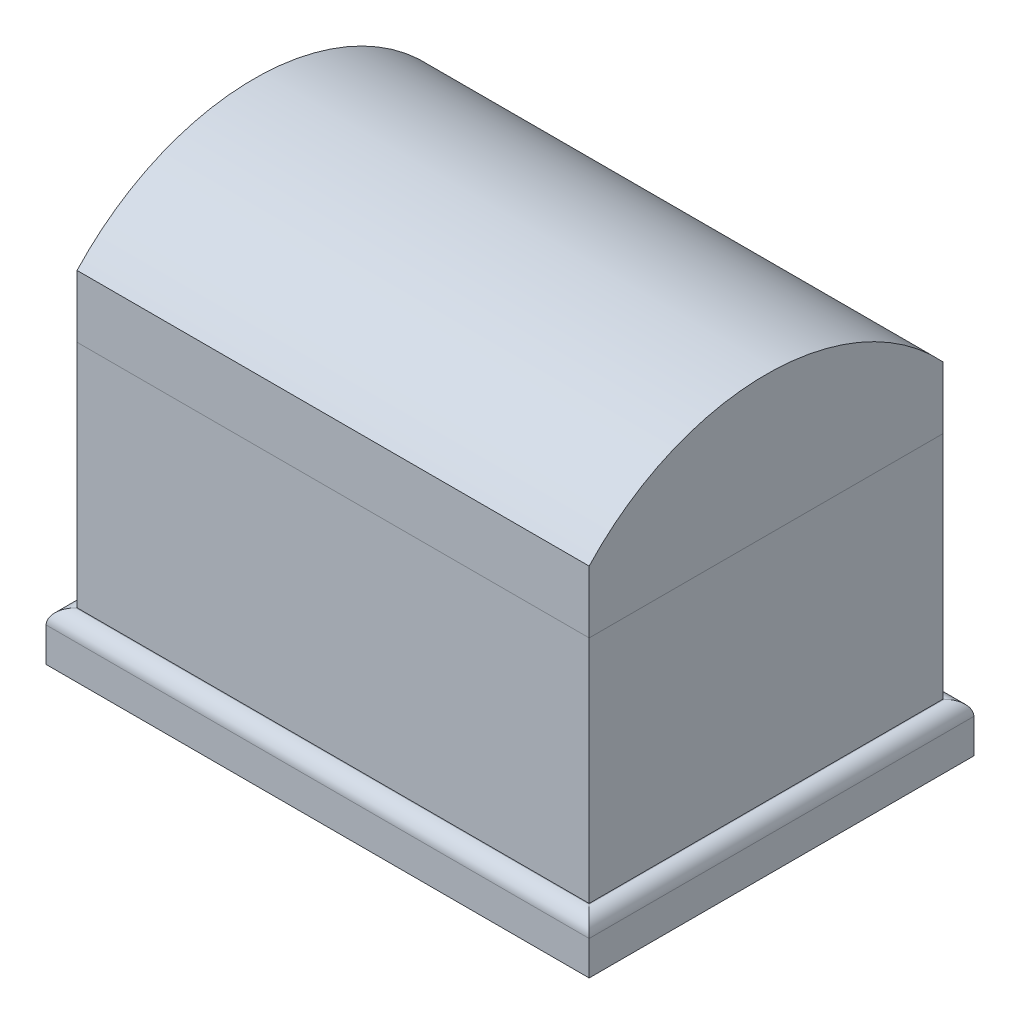
SolidWorks part; units mm, degrees
ref_plane "Front Plane" through (0, 0, 0) normal (0, 0, 1) x (1, 0, 0)
ref_plane "Top Plane" through (0, 0, 0) normal (0, 1, 0) x (1, 0, 0)
ref_plane "Right Plane" through (0, 0, 0) normal (1, 0, 0) x (0, 0, -1)
sketch "Sketch1" plane through (0, 0, 0) normal (0, 1, 0) x (1, 0, 0)
  line L1 (-78.867, -54.483) -> (78.867, -54.483)
  line L2 (-78.867, -54.483) -> (-78.867, 54.483)
  line L3 (-78.867, 54.483) -> (78.867, 54.483)
  line L4 (78.867, -54.483) -> (78.867, 54.483)
  line L5 (-78.867, -54.483) -> (78.867, 54.483) construction
  line L6 (-78.867, 54.483) -> (78.867, -54.483) construction
  point P0 (0, 0)
  dimension "D1" = 157.734
  dimension "D2" = 108.966
extrude "Boss-Extrude1" add sketch "Sketch1" along normal blind 114.1349
sketch "Sketch2" plane through (0, 0, 54.483) normal (0, 0, 1) x (1, 0, 0)
  line L0 (-78.867, 0) -> (-79.0575, 0)
  line L1 (-83.6295, -4.572) -> (-83.6295, -15.113)
  line L2 (-83.6295, -15.113) -> (-73.7235, -15.113)
  line L3 (-73.7235, -15.113) -> (-73.7235, 0)
  line L4 (-78.867, 0) -> (78.867, 0) construction
  line L5 (-73.7235, 0) -> (-78.867, 0)
  arc A0 (-79.0575, 0) -> (-83.6295, -4.572) centre (-79.0575, -4.572) ccw
  point P11 (-83.6295, 0)
  dimension "D4" = 4.572
  dimension "D1" = 9.906
  dimension "D2" = 4.7625
  dimension "D3" = 15.113
sketch "Sketch3" plane through (0, 0, 0) normal (0, -1, 0) x (1, 0, 0)
  line L4 (78.867, -54.483) -> (78.867, 54.483)
  line L5 (78.867, 54.483) -> (-78.867, 54.483)
  line L6 (-78.867, 54.483) -> (-78.867, -54.483)
  line L7 (-78.867, -54.483) -> (78.867, -54.483)
  line L8 (78.867, -54.483) -> (78.867, 54.483)
  line L9 (78.867, 54.483) -> (-78.867, 54.483)
  line L10 (-78.867, 54.483) -> (-78.867, -54.483)
  line L11 (-78.867, -54.483) -> (78.867, -54.483)
  dimension "D1" = 0
sweep "Sweep1" add profiles "Sketch2" path "Sketch3"
sketch "Sketch4" plane through (-78.867, 0, 0) normal (-1, 0, 0) x (0, 0, 1)
  line L0 (-54.483, 114.1349) -> (-54.483, 0) construction
  line L1 (54.483, 114.1349) -> (54.483, 0) construction
  line L2 (-54.483, 114.1349) -> (54.483, 114.1349) construction
  line L3 (-54.483, 90.0049) -> (-54.483, 114.1349)
  line L4 (-54.483, 114.1349) -> (54.483, 114.1349)
  line L5 (54.483, 114.1349) -> (54.483, 90.0049)
  arc A0 (-54.483, 90.0049) -> (54.483, 90.0049) centre (0, 39.7801) cw
  dimension "D2" = 0.254
  dimension "D1" = 24.13
extrude "Cut-Extrude1" cut sketch "Sketch4" against normal through all
ref_plane "Plane1" through (0, 90.0049, 0) normal (0, 1, 0) x (1, 0, 0)
ref_plane "Plane2" through (0, 70.8406, 0) normal (0, 1, 0) x (1, 0, 0)
split "Split1" trim tools "Plane2" bodies to split 103 resulting bodies 104 105
shell "Shell1" thickness 7.0104 removed face at (0, 70.8406, 0)
shell "Shell2" thickness 7.0104 removed face at (0, 70.8406, 0)
